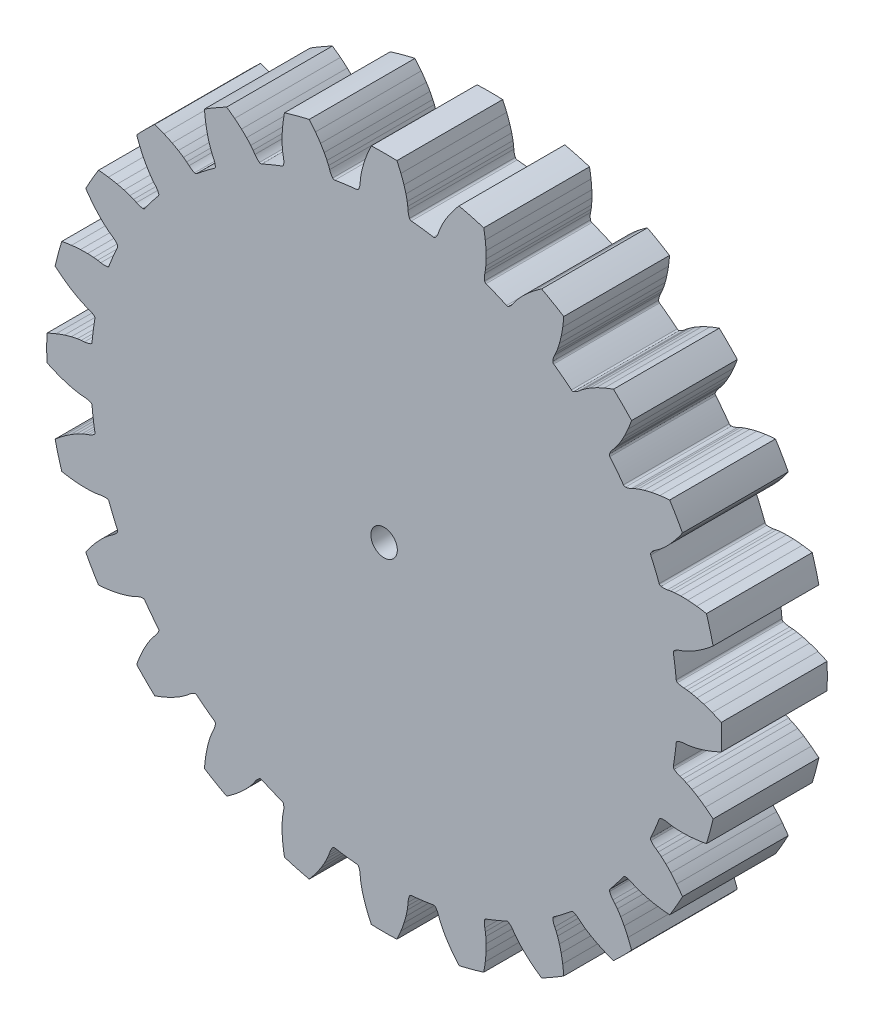
SolidWorks part; units mm, degrees
ref_plane "Front Plane" through (0, 0, 0) normal (0, 0, 1) x (1, 0, 0)
ref_plane "Top Plane" through (0, 0, 0) normal (0, 1, 0) x (1, 0, 0)
ref_plane "Right Plane" through (0, 0, 0) normal (1, 0, 0) x (0, 0, -1)
sketch "Model" plane through (0, 0, 0) normal (0, 0, 1) x (1, 0, 0)
  arc A1 (34.9181, -4.5971) -> (35.0673, -3.2696) centre (0, 0) ccw
  arc A2 (35.2278, -3.0481) -> (35.0673, -3.2696) centre (35.3347, -3.2945) ccw
  arc A3 (35.9833, -2.8721) -> (35.2278, -3.0481) centre (36.0877, -5.0299) ccw
  arc A4 (35.9833, -2.8721) -> (36.3636, -2.8405) centre (35.7172, 2.6237) ccw
  arc A5 (36.3636, -2.8405) -> (36.8336, -2.7716) centre (35.3622, 5.6245) ccw
  arc A6 (36.8336, -2.7716) -> (37.5555, -2.6174) centre (35.1043, 7.0963) ccw
  arc A7 (37.5555, -2.6174) -> (38.3737, -2.3829) centre (34.2966, 10.2971) ccw
  arc A8 (38.3737, -2.3829) -> (39.3866, -2.0164) centre (33.8084, 11.8154) ccw
  arc A9 (39.3866, -2.0164) -> (40.4752, -1.5354) centre (32.5769, 14.869) ccw
  arc A10 (40.4752, -1.5354) -> (40.4752, 1.5354) centre (0, 0) ccw
  arc A11 (40.4752, 1.5354) -> (39.3866, 2.0164) centre (32.5769, -14.869) ccw
  arc A12 (39.3866, 2.0164) -> (38.3737, 2.3829) centre (33.8084, -11.8154) ccw
  arc A13 (38.3737, 2.3829) -> (37.5555, 2.6174) centre (34.2966, -10.2971) ccw
  arc A14 (37.5555, 2.6174) -> (36.8336, 2.7716) centre (35.1043, -7.0963) ccw
  arc A15 (36.8336, 2.7716) -> (36.3636, 2.8405) centre (35.3622, -5.6245) ccw
  arc A16 (36.3636, 2.8405) -> (35.9833, 2.8721) centre (35.7172, -2.6237) ccw
  arc A17 (35.2278, 3.0481) -> (35.9833, 2.8721) centre (36.0877, 5.0299) ccw
  arc A18 (35.0673, 3.2696) -> (35.2278, 3.0481) centre (35.3347, 3.2945) ccw
  arc A19 (35.0673, 3.2696) -> (34.7187, 5.9179) centre (0, 0) ccw
  arc A20 (34.8164, 6.1734) -> (34.7187, 5.9179) centre (34.9834, 5.9631) ccw
  arc A21 (35.5005, 6.5389) -> (34.8164, 6.1734) centre (36.1599, 4.4817) ccw
  arc A22 (35.5005, 6.5389) -> (35.8597, 6.6679) centre (33.8211, 11.7785) ccw
  arc A23 (35.8597, 6.6679) -> (36.2958, 6.8561) centre (32.7015, 14.5853) ccw
  arc A24 (36.2958, 6.8561) -> (36.9533, 7.1918) centre (32.0715, 15.9402) ccw
  arc A25 (36.9533, 7.1918) -> (37.6829, 7.6301) centre (30.4629, 18.8229) ccw
  arc A26 (37.6829, 7.6301) -> (38.5664, 8.2463) centre (29.5984, 20.1631) ccw
  arc A27 (38.5664, 8.2463) -> (39.4934, 8.9927) centre (27.6185, 22.7939) ccw
  arc A28 (39.4934, 8.9927) -> (38.6987, 11.9589) centre (0, 0) ccw
  arc A29 (38.6987, 11.9589) -> (37.5227, 12.1417) centre (35.3153, -5.9309) ccw
  arc A30 (37.5227, 12.1417) -> (36.4494, 12.2336) centre (35.7145, -2.6625) ccw
  arc A31 (36.4494, 12.2336) -> (35.5984, 12.2483) centre (35.7931, -1.0696) ccw
  arc A32 (35.5984, 12.2483) -> (34.8612, 12.2104) centre (35.7448, 2.2311) ccw
  arc A33 (34.8612, 12.2104) -> (34.3894, 12.1553) centre (35.613, 3.7195) ccw
  arc A34 (34.3894, 12.1553) -> (34.0138, 12.0874) centre (35.1792, 6.71) ccw
  arc A35 (33.2386, 12.0619) -> (34.0138, 12.0874) centre (33.5562, 14.1987) ccw
  arc A36 (33.0262, 12.2343) -> (33.2386, 12.0619) centre (33.2781, 12.3275) ccw
  arc A37 (33.0262, 12.2343) -> (32.004, 14.7021) centre (0, 0) ccw
  arc A38 (32.0323, 14.9742) -> (32.004, 14.7021) centre (32.248, 14.8142) ccw
  arc A39 (32.5985, 15.5043) -> (32.0323, 14.9742) centre (33.7678, 13.6878) ccw
  arc A40 (32.5985, 15.5043) -> (32.912, 15.7219) centre (29.6202, 20.1308) ccw
  arc A41 (32.912, 15.7219) -> (33.2846, 16.0165) centre (27.8123, 22.5521) ccw
  arc A42 (33.2846, 16.0165) -> (33.8327, 16.511) centre (26.853, 23.6978) ccw
  arc A43 (33.8327, 16.511) -> (34.4241, 17.1232) centre (24.5532, 26.0659) ccw
  arc A44 (34.4241, 17.1232) -> (35.118, 17.9471) centre (23.3712, 27.1366) ccw
  arc A45 (35.118, 17.9471) -> (35.8203, 18.9079) centre (20.7779, 29.1654) ccw
  arc A46 (35.8203, 18.9079) -> (34.2849, 21.5673) centre (0, 0) ccw
  arc A47 (34.2849, 21.5673) -> (33.1016, 21.4395) centre (35.647, 3.4115) ccw
  arc A48 (33.1016, 21.4395) -> (32.0412, 21.2505) centre (35.1866, 6.6718) ccw
  arc A49 (32.0412, 21.2505) -> (31.2153, 21.0445) centre (34.8503, 8.2307) ccw
  arc A50 (31.2153, 21.0445) -> (30.513, 20.817) centre (33.9494, 11.4065) ccw
  arc A51 (30.513, 20.817) -> (30.0715, 20.6417) centre (33.4369, 12.8101) ccw
  arc A52 (30.0715, 20.6417) -> (29.7263, 20.479) centre (32.2438, 15.5865) ccw
  arc A53 (28.9841, 20.2537) -> (29.7263, 20.479) centre (28.7379, 22.3999) ccw
  arc A54 (28.7344, 20.3652) -> (28.9841, 20.2537) centre (28.9535, 20.5205) ccw
  arc A55 (28.7344, 20.3652) -> (27.1083, 22.4844) centre (0, 0) ccw
  arc A56 (27.0652, 22.7545) -> (27.1083, 22.4844) centre (27.315, 22.6559) ccw
  arc A57 (27.4749, 23.4131) -> (27.0652, 22.7545) centre (29.0746, 21.9612) ccw
  arc A58 (27.4749, 23.4131) -> (27.7215, 23.7044) centre (23.4007, 27.1111) ccw
  arc A59 (27.7215, 23.7044) -> (28.0051, 24.0855) centre (21.0277, 28.982) ccw
  arc A60 (28.0051, 24.0855) -> (28.4066, 24.7049) centre (19.8046, 29.8404) ccw
  arc A61 (28.4066, 24.7049) -> (28.8193, 25.4493) centre (16.9702, 31.5325) ccw
  arc A62 (28.8193, 25.4493) -> (29.2763, 26.4247) centre (15.5514, 32.2609) ccw
  arc A63 (29.2763, 26.4247) -> (29.706, 27.5346) centre (12.5214, 33.5494) ccw
  arc A64 (29.706, 27.5346) -> (27.5346, 29.706) centre (0, 0) ccw
  arc A65 (27.5346, 29.706) -> (26.4247, 29.2763) centre (33.5494, 12.5214) ccw
  arc A66 (26.4247, 29.2763) -> (25.4493, 28.8193) centre (32.2609, 15.5514) ccw
  arc A67 (25.4493, 28.8193) -> (24.7049, 28.4066) centre (31.5325, 16.9702) ccw
  arc A68 (24.7049, 28.4066) -> (24.0855, 28.0051) centre (29.8404, 19.8046) ccw
  arc A69 (24.0855, 28.0051) -> (23.7044, 27.7215) centre (28.982, 21.0277) ccw
  arc A70 (23.7044, 27.7215) -> (23.4131, 27.4749) centre (27.1111, 23.4007) ccw
  arc A71 (22.7545, 27.0652) -> (23.4131, 27.4749) centre (21.9612, 29.0746) ccw
  arc A72 (22.4844, 27.1083) -> (22.7545, 27.0652) centre (22.6559, 27.315) ccw
  arc A73 (22.4844, 27.1083) -> (20.3652, 28.7344) centre (0, 0) ccw
  arc A74 (20.2537, 28.9841) -> (20.3652, 28.7344) centre (20.5205, 28.9535) ccw
  arc A75 (20.479, 29.7263) -> (20.2537, 28.9841) centre (22.3999, 28.7379) ccw
  arc A76 (20.479, 29.7263) -> (20.6417, 30.0715) centre (15.5865, 32.2438) ccw
  arc A77 (20.6417, 30.0715) -> (20.817, 30.513) centre (12.8101, 33.4369) ccw
  arc A78 (20.817, 30.513) -> (21.0445, 31.2153) centre (11.4065, 33.9494) ccw
  arc A79 (21.0445, 31.2153) -> (21.2505, 32.0412) centre (8.2307, 34.8503) ccw
  arc A80 (21.2505, 32.0412) -> (21.4395, 33.1016) centre (6.6718, 35.1866) ccw
  arc A81 (21.4395, 33.1016) -> (21.5673, 34.2849) centre (3.4115, 35.647) ccw
  arc A82 (21.5673, 34.2849) -> (18.9079, 35.8203) centre (0, 0) ccw
  arc A83 (18.9079, 35.8203) -> (17.9471, 35.118) centre (29.1654, 20.7779) ccw
  arc A84 (17.9471, 35.118) -> (17.1232, 34.4241) centre (27.1366, 23.3712) ccw
  arc A85 (17.1232, 34.4241) -> (16.511, 33.8327) centre (26.0659, 24.5532) ccw
  arc A86 (16.511, 33.8327) -> (16.0165, 33.2846) centre (23.6978, 26.853) ccw
  arc A87 (16.0165, 33.2846) -> (15.7219, 32.912) centre (22.5521, 27.8123) ccw
  arc A88 (15.7219, 32.912) -> (15.5043, 32.5985) centre (20.1308, 29.6202) ccw
  arc A89 (14.9742, 32.0323) -> (15.5043, 32.5985) centre (13.6878, 33.7678) ccw
  arc A90 (14.7021, 32.004) -> (14.9742, 32.0323) centre (14.8142, 32.248) ccw
  arc A91 (14.7021, 32.004) -> (12.2343, 33.0262) centre (0, 0) ccw
  arc A92 (12.0619, 33.2386) -> (12.2343, 33.0262) centre (12.3275, 33.2781) ccw
  arc A93 (12.0874, 34.0138) -> (12.0619, 33.2386) centre (14.1987, 33.5562) ccw
  arc A94 (12.0874, 34.0138) -> (12.1553, 34.3894) centre (6.71, 35.1792) ccw
  arc A95 (12.1553, 34.3894) -> (12.2104, 34.8612) centre (3.7195, 35.613) ccw
  arc A96 (12.2104, 34.8612) -> (12.2483, 35.5984) centre (2.2311, 35.7448) ccw
  arc A97 (12.2483, 35.5984) -> (12.2336, 36.4494) centre (-1.0696, 35.7931) ccw
  arc A98 (12.2336, 36.4494) -> (12.1417, 37.5227) centre (-2.6625, 35.7145) ccw
  arc A99 (12.1417, 37.5227) -> (11.9589, 38.6987) centre (-5.9309, 35.3153) ccw
  arc A100 (11.9589, 38.6987) -> (8.9927, 39.4934) centre (0, 0) ccw
  arc A101 (8.9927, 39.4934) -> (8.2463, 38.5664) centre (22.7939, 27.6185) ccw
  arc A102 (8.2463, 38.5664) -> (7.6301, 37.6829) centre (20.1631, 29.5984) ccw
  arc A103 (7.6301, 37.6829) -> (7.1918, 36.9533) centre (18.8229, 30.4629) ccw
  arc A104 (7.1918, 36.9533) -> (6.8561, 36.2958) centre (15.9402, 32.0715) ccw
  arc A105 (6.8561, 36.2958) -> (6.6679, 35.8597) centre (14.5853, 32.7015) ccw
  arc A106 (6.6679, 35.8597) -> (6.5389, 35.5005) centre (11.7785, 33.8211) ccw
  arc A107 (6.1734, 34.8164) -> (6.5389, 35.5005) centre (4.4817, 36.1599) ccw
  arc A108 (5.9179, 34.7187) -> (6.1734, 34.8164) centre (5.9631, 34.9834) ccw
  arc A109 (5.9179, 34.7187) -> (3.2696, 35.0673) centre (0, 0) ccw
  arc A110 (3.0481, 35.2278) -> (3.2696, 35.0673) centre (3.2945, 35.3347) ccw
  arc A111 (2.8721, 35.9833) -> (3.0481, 35.2278) centre (5.0299, 36.0877) ccw
  arc A112 (2.8721, 35.9833) -> (2.8405, 36.3636) centre (-2.6237, 35.7172) ccw
  arc A113 (2.8405, 36.3636) -> (2.7716, 36.8336) centre (-5.6245, 35.3622) ccw
  arc A114 (2.7716, 36.8336) -> (2.6174, 37.5555) centre (-7.0963, 35.1043) ccw
  arc A115 (2.6174, 37.5555) -> (2.3829, 38.3737) centre (-10.2971, 34.2966) ccw
  arc A116 (2.3829, 38.3737) -> (2.0164, 39.3866) centre (-11.8154, 33.8084) ccw
  arc A117 (2.0164, 39.3866) -> (1.5354, 40.4752) centre (-14.869, 32.5769) ccw
  arc A118 (1.5354, 40.4752) -> (-1.5354, 40.4752) centre (0, 0) ccw
  arc A119 (-1.5354, 40.4752) -> (-2.0164, 39.3866) centre (14.869, 32.5769) ccw
  arc A120 (-2.0164, 39.3866) -> (-2.3829, 38.3737) centre (11.8154, 33.8084) ccw
  arc A121 (-2.3829, 38.3737) -> (-2.6174, 37.5555) centre (10.2971, 34.2966) ccw
  arc A122 (-2.6174, 37.5555) -> (-2.7716, 36.8336) centre (7.0963, 35.1043) ccw
  arc A123 (-2.7716, 36.8336) -> (-2.8405, 36.3636) centre (5.6245, 35.3622) ccw
  arc A124 (-2.8405, 36.3636) -> (-2.8721, 35.9833) centre (2.6237, 35.7172) ccw
  arc A125 (-3.0481, 35.2278) -> (-2.8721, 35.9833) centre (-5.0299, 36.0877) ccw
  arc A126 (-3.2696, 35.0673) -> (-3.0481, 35.2278) centre (-3.2945, 35.3347) ccw
  arc A127 (-3.2696, 35.0673) -> (-5.9179, 34.7187) centre (0, 0) ccw
  arc A128 (-6.1734, 34.8164) -> (-5.9179, 34.7187) centre (-5.9631, 34.9834) ccw
  arc A129 (-6.5389, 35.5005) -> (-6.1734, 34.8164) centre (-4.4817, 36.1599) ccw
  arc A130 (-6.5389, 35.5005) -> (-6.6679, 35.8597) centre (-11.7785, 33.8211) ccw
  arc A131 (-6.6679, 35.8597) -> (-6.8561, 36.2958) centre (-14.5853, 32.7015) ccw
  arc A132 (-6.8561, 36.2958) -> (-7.1918, 36.9533) centre (-15.9402, 32.0715) ccw
  arc A133 (-7.1918, 36.9533) -> (-7.6301, 37.6829) centre (-18.8229, 30.4629) ccw
  arc A134 (-7.6301, 37.6829) -> (-8.2463, 38.5664) centre (-20.1631, 29.5984) ccw
  arc A135 (-8.2463, 38.5664) -> (-8.9927, 39.4934) centre (-22.7939, 27.6185) ccw
  arc A136 (-8.9927, 39.4934) -> (-11.9589, 38.6987) centre (0, 0) ccw
  arc A137 (-11.9589, 38.6987) -> (-12.1417, 37.5227) centre (5.9309, 35.3153) ccw
  arc A138 (-12.1417, 37.5227) -> (-12.2336, 36.4494) centre (2.6625, 35.7145) ccw
  arc A139 (-12.2336, 36.4494) -> (-12.2483, 35.5984) centre (1.0696, 35.7931) ccw
  arc A140 (-12.2483, 35.5984) -> (-12.2104, 34.8612) centre (-2.2311, 35.7448) ccw
  arc A141 (-12.2104, 34.8612) -> (-12.1553, 34.3894) centre (-3.7195, 35.613) ccw
  arc A142 (-12.1553, 34.3894) -> (-12.0874, 34.0138) centre (-6.71, 35.1792) ccw
  arc A143 (-12.0619, 33.2386) -> (-12.0874, 34.0138) centre (-14.1987, 33.5562) ccw
  arc A144 (-12.2343, 33.0262) -> (-12.0619, 33.2386) centre (-12.3275, 33.2781) ccw
  arc A145 (-12.2343, 33.0262) -> (-14.7021, 32.004) centre (0, 0) ccw
  arc A146 (-14.9742, 32.0323) -> (-14.7021, 32.004) centre (-14.8142, 32.248) ccw
  arc A147 (-15.5043, 32.5985) -> (-14.9742, 32.0323) centre (-13.6878, 33.7678) ccw
  arc A148 (-15.5043, 32.5985) -> (-15.7219, 32.912) centre (-20.1308, 29.6202) ccw
  arc A149 (-15.7219, 32.912) -> (-16.0165, 33.2846) centre (-22.5521, 27.8123) ccw
  arc A150 (-16.0165, 33.2846) -> (-16.511, 33.8327) centre (-23.6978, 26.853) ccw
  arc A151 (-16.511, 33.8327) -> (-17.1232, 34.4241) centre (-26.0659, 24.5532) ccw
  arc A152 (-17.1232, 34.4241) -> (-17.9471, 35.118) centre (-27.1366, 23.3712) ccw
  arc A153 (-17.9471, 35.118) -> (-18.9079, 35.8203) centre (-29.1654, 20.7779) ccw
  arc A154 (-18.9079, 35.8203) -> (-21.5673, 34.2849) centre (0, 0) ccw
  arc A155 (-21.5673, 34.2849) -> (-21.4395, 33.1016) centre (-3.4115, 35.647) ccw
  arc A156 (-21.4395, 33.1016) -> (-21.2505, 32.0412) centre (-6.6718, 35.1866) ccw
  arc A157 (-21.2505, 32.0412) -> (-21.0445, 31.2153) centre (-8.2307, 34.8503) ccw
  arc A158 (-21.0445, 31.2153) -> (-20.817, 30.513) centre (-11.4065, 33.9494) ccw
  arc A159 (-20.817, 30.513) -> (-20.6417, 30.0715) centre (-12.8101, 33.4369) ccw
  arc A160 (-20.6417, 30.0715) -> (-20.479, 29.7263) centre (-15.5865, 32.2438) ccw
  arc A161 (-20.2537, 28.9841) -> (-20.479, 29.7263) centre (-22.3999, 28.7379) ccw
  arc A162 (-20.3652, 28.7344) -> (-20.2537, 28.9841) centre (-20.5205, 28.9535) ccw
  arc A163 (-20.3652, 28.7344) -> (-22.4844, 27.1083) centre (0, 0) ccw
  arc A164 (-22.7545, 27.0652) -> (-22.4844, 27.1083) centre (-22.6559, 27.315) ccw
  arc A165 (-23.4131, 27.4749) -> (-22.7545, 27.0652) centre (-21.9612, 29.0746) ccw
  arc A166 (-23.4131, 27.4749) -> (-23.7044, 27.7215) centre (-27.1111, 23.4007) ccw
  arc A167 (-23.7044, 27.7215) -> (-24.0855, 28.0051) centre (-28.982, 21.0277) ccw
  arc A168 (-24.0855, 28.0051) -> (-24.7049, 28.4066) centre (-29.8404, 19.8046) ccw
  arc A169 (-24.7049, 28.4066) -> (-25.4493, 28.8193) centre (-31.5325, 16.9702) ccw
  arc A170 (-25.4493, 28.8193) -> (-26.4247, 29.2763) centre (-32.2609, 15.5514) ccw
  arc A171 (-26.4247, 29.2763) -> (-27.5346, 29.706) centre (-33.5494, 12.5214) ccw
  arc A172 (-27.5346, 29.706) -> (-29.706, 27.5346) centre (0, 0) ccw
  arc A173 (-29.706, 27.5346) -> (-29.2763, 26.4247) centre (-12.5214, 33.5494) ccw
  arc A174 (-29.2763, 26.4247) -> (-28.8193, 25.4493) centre (-15.5514, 32.2609) ccw
  arc A175 (-28.8193, 25.4493) -> (-28.4066, 24.7049) centre (-16.9702, 31.5325) ccw
  arc A176 (-28.4066, 24.7049) -> (-28.0051, 24.0855) centre (-19.8046, 29.8404) ccw
  arc A177 (-28.0051, 24.0855) -> (-27.7215, 23.7044) centre (-21.0277, 28.982) ccw
  arc A178 (-27.7215, 23.7044) -> (-27.4749, 23.4131) centre (-23.4007, 27.1111) ccw
  arc A179 (-27.0652, 22.7545) -> (-27.4749, 23.4131) centre (-29.0746, 21.9612) ccw
  arc A180 (-27.1083, 22.4844) -> (-27.0652, 22.7545) centre (-27.315, 22.6559) ccw
  arc A181 (-27.1083, 22.4844) -> (-28.7344, 20.3652) centre (0, 0) ccw
  arc A182 (-28.9841, 20.2537) -> (-28.7344, 20.3652) centre (-28.9535, 20.5205) ccw
  arc A183 (-29.7263, 20.479) -> (-28.9841, 20.2537) centre (-28.7379, 22.3999) ccw
  arc A184 (-29.7263, 20.479) -> (-30.0715, 20.6417) centre (-32.2438, 15.5865) ccw
  arc A185 (-30.0715, 20.6417) -> (-30.513, 20.817) centre (-33.4369, 12.8101) ccw
  arc A186 (-30.513, 20.817) -> (-31.2153, 21.0445) centre (-33.9494, 11.4065) ccw
  arc A187 (-31.2153, 21.0445) -> (-32.0412, 21.2505) centre (-34.8503, 8.2307) ccw
  arc A188 (-32.0412, 21.2505) -> (-33.1016, 21.4395) centre (-35.1866, 6.6718) ccw
  arc A189 (-33.1016, 21.4395) -> (-34.2849, 21.5673) centre (-35.647, 3.4115) ccw
  arc A190 (-34.2849, 21.5673) -> (-35.8203, 18.9079) centre (0, 0) ccw
  arc A191 (-35.8203, 18.9079) -> (-35.118, 17.9471) centre (-20.7779, 29.1654) ccw
  arc A192 (-35.118, 17.9471) -> (-34.4241, 17.1232) centre (-23.3712, 27.1366) ccw
  arc A193 (-34.4241, 17.1232) -> (-33.8327, 16.511) centre (-24.5532, 26.0659) ccw
  arc A194 (-33.8327, 16.511) -> (-33.2846, 16.0165) centre (-26.853, 23.6978) ccw
  arc A195 (-33.2846, 16.0165) -> (-32.912, 15.7219) centre (-27.8123, 22.5521) ccw
  arc A196 (-32.912, 15.7219) -> (-32.5985, 15.5043) centre (-29.6202, 20.1308) ccw
  arc A197 (-32.0323, 14.9742) -> (-32.5985, 15.5043) centre (-33.7678, 13.6878) ccw
  arc A198 (-32.004, 14.7021) -> (-32.0323, 14.9742) centre (-32.248, 14.8142) ccw
  arc A199 (-32.004, 14.7021) -> (-33.0262, 12.2343) centre (0, 0) ccw
  arc A200 (-33.2386, 12.0619) -> (-33.0262, 12.2343) centre (-33.2781, 12.3275) ccw
  arc A201 (-34.0138, 12.0874) -> (-33.2386, 12.0619) centre (-33.5562, 14.1987) ccw
  arc A202 (-34.0138, 12.0874) -> (-34.3894, 12.1553) centre (-35.1792, 6.71) ccw
  arc A203 (-34.3894, 12.1553) -> (-34.8612, 12.2104) centre (-35.613, 3.7195) ccw
  arc A204 (-34.8612, 12.2104) -> (-35.5984, 12.2483) centre (-35.7448, 2.2311) ccw
  arc A205 (-35.5984, 12.2483) -> (-36.4494, 12.2336) centre (-35.7931, -1.0696) ccw
  arc A206 (-36.4494, 12.2336) -> (-37.5227, 12.1417) centre (-35.7145, -2.6625) ccw
  arc A207 (-37.5227, 12.1417) -> (-38.6987, 11.9589) centre (-35.3153, -5.9309) ccw
  arc A208 (-38.6987, 11.9589) -> (-39.4934, 8.9927) centre (0, 0) ccw
  arc A209 (-39.4934, 8.9927) -> (-38.5664, 8.2463) centre (-27.6185, 22.7939) ccw
  arc A210 (-38.5664, 8.2463) -> (-37.6829, 7.6301) centre (-29.5984, 20.1631) ccw
  arc A211 (-37.6829, 7.6301) -> (-36.9533, 7.1918) centre (-30.4629, 18.8229) ccw
  arc A212 (-36.9533, 7.1918) -> (-36.2958, 6.8561) centre (-32.0715, 15.9402) ccw
  arc A213 (-36.2958, 6.8561) -> (-35.8597, 6.6679) centre (-32.7015, 14.5853) ccw
  arc A214 (-35.8597, 6.6679) -> (-35.5005, 6.5389) centre (-33.8211, 11.7785) ccw
  arc A215 (-34.8164, 6.1734) -> (-35.5005, 6.5389) centre (-36.1599, 4.4817) ccw
  arc A216 (-34.7187, 5.9179) -> (-34.8164, 6.1734) centre (-34.9834, 5.9631) ccw
  arc A217 (-34.7187, 5.9179) -> (-35.0673, 3.2696) centre (0, 0) ccw
  arc A218 (-35.2278, 3.0481) -> (-35.0673, 3.2696) centre (-35.3347, 3.2945) ccw
  arc A219 (-35.9833, 2.8721) -> (-35.2278, 3.0481) centre (-36.0877, 5.0299) ccw
  arc A220 (-35.9833, 2.8721) -> (-36.3636, 2.8405) centre (-35.7172, -2.6237) ccw
  arc A221 (-36.3636, 2.8405) -> (-36.8336, 2.7716) centre (-35.3622, -5.6245) ccw
  arc A222 (-36.8336, 2.7716) -> (-37.5555, 2.6174) centre (-35.1043, -7.0963) ccw
  arc A223 (-37.5555, 2.6174) -> (-38.3737, 2.3829) centre (-34.2966, -10.2971) ccw
  arc A224 (-38.3737, 2.3829) -> (-39.3866, 2.0164) centre (-33.8084, -11.8154) ccw
  arc A225 (-39.3866, 2.0164) -> (-40.4752, 1.5354) centre (-32.5769, -14.869) ccw
  arc A226 (-40.4752, 1.5354) -> (-40.4752, -1.5354) centre (0, 0) ccw
  arc A227 (-40.4752, -1.5354) -> (-39.3866, -2.0164) centre (-32.5769, 14.869) ccw
  arc A228 (-39.3866, -2.0164) -> (-38.3737, -2.3829) centre (-33.8084, 11.8154) ccw
  arc A229 (-38.3737, -2.3829) -> (-37.5555, -2.6174) centre (-34.2966, 10.2971) ccw
  arc A230 (-37.5555, -2.6174) -> (-36.8336, -2.7716) centre (-35.1043, 7.0963) ccw
  arc A231 (-36.8336, -2.7716) -> (-36.3636, -2.8405) centre (-35.3622, 5.6245) ccw
  arc A232 (-36.3636, -2.8405) -> (-35.9833, -2.8721) centre (-35.7172, 2.6237) ccw
  arc A233 (-35.2278, -3.0481) -> (-35.9833, -2.8721) centre (-36.0877, -5.0299) ccw
  arc A234 (-35.0673, -3.2696) -> (-35.2278, -3.0481) centre (-35.3347, -3.2945) ccw
  arc A235 (-35.0673, -3.2696) -> (-34.7187, -5.9179) centre (0, 0) ccw
  arc A236 (-34.8164, -6.1734) -> (-34.7187, -5.9179) centre (-34.9834, -5.9631) ccw
  arc A237 (-35.5005, -6.5389) -> (-34.8164, -6.1734) centre (-36.1599, -4.4817) ccw
  arc A238 (-35.5005, -6.5389) -> (-35.8597, -6.6679) centre (-33.8211, -11.7785) ccw
  arc A239 (-35.8597, -6.6679) -> (-36.2958, -6.8561) centre (-32.7015, -14.5853) ccw
  arc A240 (-36.2958, -6.8561) -> (-36.9533, -7.1918) centre (-32.0715, -15.9402) ccw
  arc A241 (-36.9533, -7.1918) -> (-37.6829, -7.6301) centre (-30.4629, -18.8229) ccw
  arc A242 (-37.6829, -7.6301) -> (-38.5664, -8.2463) centre (-29.5984, -20.1631) ccw
  arc A243 (-38.5664, -8.2463) -> (-39.4934, -8.9927) centre (-27.6185, -22.7939) ccw
  arc A244 (-39.4934, -8.9927) -> (-38.6987, -11.9589) centre (0, 0) ccw
  arc A245 (-38.6987, -11.9589) -> (-37.5227, -12.1417) centre (-35.3153, 5.9309) ccw
  arc A246 (-37.5227, -12.1417) -> (-36.4494, -12.2336) centre (-35.7145, 2.6625) ccw
  arc A247 (-36.4494, -12.2336) -> (-35.5984, -12.2483) centre (-35.7931, 1.0696) ccw
  arc A248 (-35.5984, -12.2483) -> (-34.8612, -12.2104) centre (-35.7448, -2.2311) ccw
  arc A249 (-34.8612, -12.2104) -> (-34.3894, -12.1553) centre (-35.613, -3.7195) ccw
  arc A250 (-34.3894, -12.1553) -> (-34.0138, -12.0874) centre (-35.1792, -6.71) ccw
  arc A251 (-33.2386, -12.0619) -> (-34.0138, -12.0874) centre (-33.5562, -14.1987) ccw
  arc A252 (-33.0262, -12.2343) -> (-33.2386, -12.0619) centre (-33.2781, -12.3275) ccw
  arc A253 (-33.0262, -12.2343) -> (-32.004, -14.7021) centre (0, 0) ccw
  arc A254 (-32.0323, -14.9742) -> (-32.004, -14.7021) centre (-32.248, -14.8142) ccw
  arc A255 (-32.5985, -15.5043) -> (-32.0323, -14.9742) centre (-33.7678, -13.6878) ccw
  arc A256 (-32.5985, -15.5043) -> (-32.912, -15.7219) centre (-29.6202, -20.1308) ccw
  arc A257 (-32.912, -15.7219) -> (-33.2846, -16.0165) centre (-27.8123, -22.5521) ccw
  arc A258 (-33.2846, -16.0165) -> (-33.8327, -16.511) centre (-26.853, -23.6978) ccw
  arc A259 (-33.8327, -16.511) -> (-34.4241, -17.1232) centre (-24.5532, -26.0659) ccw
  arc A260 (-34.4241, -17.1232) -> (-35.118, -17.9471) centre (-23.3712, -27.1366) ccw
  arc A261 (-35.118, -17.9471) -> (-35.8203, -18.9079) centre (-20.7779, -29.1654) ccw
  arc A262 (-35.8203, -18.9079) -> (-34.2849, -21.5673) centre (0, 0) ccw
  arc A263 (-34.2849, -21.5673) -> (-33.1016, -21.4395) centre (-35.647, -3.4115) ccw
  arc A264 (-33.1016, -21.4395) -> (-32.0412, -21.2505) centre (-35.1866, -6.6718) ccw
  arc A265 (-32.0412, -21.2505) -> (-31.2153, -21.0445) centre (-34.8503, -8.2307) ccw
  arc A266 (-31.2153, -21.0445) -> (-30.513, -20.817) centre (-33.9494, -11.4065) ccw
  arc A267 (-30.513, -20.817) -> (-30.0715, -20.6417) centre (-33.4369, -12.8101) ccw
  arc A268 (-30.0715, -20.6417) -> (-29.7263, -20.479) centre (-32.2438, -15.5865) ccw
  arc A269 (-28.9841, -20.2537) -> (-29.7263, -20.479) centre (-28.7379, -22.3999) ccw
  arc A270 (-28.7344, -20.3652) -> (-28.9841, -20.2537) centre (-28.9535, -20.5205) ccw
  arc A271 (-28.7344, -20.3652) -> (-27.1083, -22.4844) centre (0, 0) ccw
  arc A272 (-27.0652, -22.7545) -> (-27.1083, -22.4844) centre (-27.315, -22.6559) ccw
  arc A273 (-27.4749, -23.4131) -> (-27.0652, -22.7545) centre (-29.0746, -21.9612) ccw
  arc A274 (-27.4749, -23.4131) -> (-27.7215, -23.7044) centre (-23.4007, -27.1111) ccw
  arc A275 (-27.7215, -23.7044) -> (-28.0051, -24.0855) centre (-21.0277, -28.982) ccw
  arc A276 (-28.0051, -24.0855) -> (-28.4066, -24.7049) centre (-19.8046, -29.8404) ccw
  arc A277 (-28.4066, -24.7049) -> (-28.8193, -25.4493) centre (-16.9702, -31.5325) ccw
  arc A278 (-28.8193, -25.4493) -> (-29.2763, -26.4247) centre (-15.5514, -32.2609) ccw
  arc A279 (-29.2763, -26.4247) -> (-29.706, -27.5346) centre (-12.5214, -33.5494) ccw
  arc A280 (-29.706, -27.5346) -> (-27.5346, -29.706) centre (0, 0) ccw
  arc A281 (-27.5346, -29.706) -> (-26.4247, -29.2763) centre (-33.5494, -12.5214) ccw
  arc A282 (-26.4247, -29.2763) -> (-25.4493, -28.8193) centre (-32.2609, -15.5514) ccw
  arc A283 (-25.4493, -28.8193) -> (-24.7049, -28.4066) centre (-31.5325, -16.9702) ccw
  arc A284 (-24.7049, -28.4066) -> (-24.0855, -28.0051) centre (-29.8404, -19.8046) ccw
  arc A285 (-24.0855, -28.0051) -> (-23.7044, -27.7215) centre (-28.982, -21.0277) ccw
  arc A286 (-23.7044, -27.7215) -> (-23.4131, -27.4749) centre (-27.1111, -23.4007) ccw
  arc A287 (-22.7545, -27.0652) -> (-23.4131, -27.4749) centre (-21.9612, -29.0746) ccw
  arc A288 (-22.4844, -27.1083) -> (-22.7545, -27.0652) centre (-22.6559, -27.315) ccw
  arc A289 (-22.4844, -27.1083) -> (-20.3652, -28.7344) centre (0, 0) ccw
  arc A290 (-20.2537, -28.9841) -> (-20.3652, -28.7344) centre (-20.5205, -28.9535) ccw
  arc A291 (-20.479, -29.7263) -> (-20.2537, -28.9841) centre (-22.3999, -28.7379) ccw
  arc A292 (-20.479, -29.7263) -> (-20.6417, -30.0715) centre (-15.5865, -32.2438) ccw
  arc A293 (-20.6417, -30.0715) -> (-20.817, -30.513) centre (-12.8101, -33.4369) ccw
  arc A294 (-20.817, -30.513) -> (-21.0445, -31.2153) centre (-11.4065, -33.9494) ccw
  arc A295 (-21.0445, -31.2153) -> (-21.2505, -32.0412) centre (-8.2307, -34.8503) ccw
  arc A296 (-21.2505, -32.0412) -> (-21.4395, -33.1016) centre (-6.6718, -35.1866) ccw
  arc A297 (-21.4395, -33.1016) -> (-21.5673, -34.2849) centre (-3.4115, -35.647) ccw
  arc A298 (-21.5673, -34.2849) -> (-18.9079, -35.8203) centre (0, 0) ccw
  arc A299 (-18.9079, -35.8203) -> (-17.9471, -35.118) centre (-29.1654, -20.7779) ccw
  arc A300 (-17.9471, -35.118) -> (-17.1232, -34.4241) centre (-27.1366, -23.3712) ccw
  arc A301 (-17.1232, -34.4241) -> (-16.511, -33.8327) centre (-26.0659, -24.5532) ccw
  arc A302 (-16.511, -33.8327) -> (-16.0165, -33.2846) centre (-23.6978, -26.853) ccw
  arc A303 (-16.0165, -33.2846) -> (-15.7219, -32.912) centre (-22.5521, -27.8123) ccw
  arc A304 (-15.7219, -32.912) -> (-15.5043, -32.5985) centre (-20.1308, -29.6202) ccw
  arc A305 (-14.9742, -32.0323) -> (-15.5043, -32.5985) centre (-13.6878, -33.7678) ccw
  arc A306 (-14.7021, -32.004) -> (-14.9742, -32.0323) centre (-14.8142, -32.248) ccw
  arc A307 (-14.7021, -32.004) -> (-12.2343, -33.0262) centre (0, 0) ccw
  arc A308 (-12.0619, -33.2386) -> (-12.2343, -33.0262) centre (-12.3275, -33.2781) ccw
  arc A309 (-12.0874, -34.0138) -> (-12.0619, -33.2386) centre (-14.1987, -33.5562) ccw
  arc A310 (-12.0874, -34.0138) -> (-12.1553, -34.3894) centre (-6.71, -35.1792) ccw
  arc A311 (-12.1553, -34.3894) -> (-12.2104, -34.8612) centre (-3.7195, -35.613) ccw
  arc A312 (-12.2104, -34.8612) -> (-12.2483, -35.5984) centre (-2.2311, -35.7448) ccw
  arc A313 (-12.2483, -35.5984) -> (-12.2336, -36.4494) centre (1.0696, -35.7931) ccw
  arc A314 (-12.2336, -36.4494) -> (-12.1417, -37.5227) centre (2.6625, -35.7145) ccw
  arc A315 (-12.1417, -37.5227) -> (-11.9589, -38.6987) centre (5.9309, -35.3153) ccw
  arc A316 (-11.9589, -38.6987) -> (-8.9927, -39.4934) centre (0, 0) ccw
  arc A317 (-8.9927, -39.4934) -> (-8.2463, -38.5664) centre (-22.7939, -27.6185) ccw
  arc A318 (-8.2463, -38.5664) -> (-7.6301, -37.6829) centre (-20.1631, -29.5984) ccw
  arc A319 (-7.6301, -37.6829) -> (-7.1918, -36.9533) centre (-18.8229, -30.4629) ccw
  arc A320 (-7.1918, -36.9533) -> (-6.8561, -36.2958) centre (-15.9402, -32.0715) ccw
  arc A321 (-6.8561, -36.2958) -> (-6.6679, -35.8597) centre (-14.5853, -32.7015) ccw
  arc A322 (-6.6679, -35.8597) -> (-6.5389, -35.5005) centre (-11.7785, -33.8211) ccw
  arc A323 (-6.1734, -34.8164) -> (-6.5389, -35.5005) centre (-4.4817, -36.1599) ccw
  arc A324 (-5.9179, -34.7187) -> (-6.1734, -34.8164) centre (-5.9631, -34.9834) ccw
  arc A325 (-5.9179, -34.7187) -> (-3.2696, -35.0673) centre (0, 0) ccw
  arc A326 (-3.0481, -35.2278) -> (-3.2696, -35.0673) centre (-3.2945, -35.3347) ccw
  arc A327 (-2.8721, -35.9833) -> (-3.0481, -35.2278) centre (-5.0299, -36.0877) ccw
  arc A328 (-2.8721, -35.9833) -> (-2.8405, -36.3636) centre (2.6237, -35.7172) ccw
  arc A329 (-2.8405, -36.3636) -> (-2.7716, -36.8336) centre (5.6245, -35.3622) ccw
  arc A330 (-2.7716, -36.8336) -> (-2.6174, -37.5555) centre (7.0963, -35.1043) ccw
  arc A331 (-2.6174, -37.5555) -> (-2.3829, -38.3737) centre (10.2971, -34.2966) ccw
  arc A332 (-2.3829, -38.3737) -> (-2.0164, -39.3866) centre (11.8154, -33.8084) ccw
  arc A333 (-2.0164, -39.3866) -> (-1.5354, -40.4752) centre (14.869, -32.5769) ccw
  arc A334 (-1.5354, -40.4752) -> (1.5354, -40.4752) centre (0, 0) ccw
  arc A335 (1.5354, -40.4752) -> (2.0164, -39.3866) centre (-14.869, -32.5769) ccw
  arc A336 (2.0164, -39.3866) -> (2.3829, -38.3737) centre (-11.8154, -33.8084) ccw
  arc A337 (2.3829, -38.3737) -> (2.6174, -37.5555) centre (-10.2971, -34.2966) ccw
  arc A338 (2.6174, -37.5555) -> (2.7716, -36.8336) centre (-7.0963, -35.1043) ccw
  arc A339 (2.7716, -36.8336) -> (2.8405, -36.3636) centre (-5.6245, -35.3622) ccw
  arc A340 (2.8405, -36.3636) -> (2.8721, -35.9833) centre (-2.6237, -35.7172) ccw
  arc A341 (3.0481, -35.2278) -> (2.8721, -35.9833) centre (5.0299, -36.0877) ccw
  arc A342 (3.2696, -35.0673) -> (3.0481, -35.2278) centre (3.2945, -35.3347) ccw
  arc A343 (3.2696, -35.0673) -> (5.9179, -34.7187) centre (0, 0) ccw
  arc A344 (6.1734, -34.8164) -> (5.9179, -34.7187) centre (5.9631, -34.9834) ccw
  arc A345 (6.5389, -35.5005) -> (6.1734, -34.8164) centre (4.4817, -36.1599) ccw
  arc A346 (6.5389, -35.5005) -> (6.6679, -35.8597) centre (11.7785, -33.8211) ccw
  arc A347 (6.6679, -35.8597) -> (6.8561, -36.2958) centre (14.5853, -32.7015) ccw
  arc A348 (6.8561, -36.2958) -> (7.1918, -36.9533) centre (15.9402, -32.0715) ccw
  arc A349 (7.1918, -36.9533) -> (7.6301, -37.6829) centre (18.8229, -30.4629) ccw
  arc A350 (7.6301, -37.6829) -> (8.2463, -38.5664) centre (20.1631, -29.5984) ccw
  arc A351 (8.2463, -38.5664) -> (8.9927, -39.4934) centre (22.7939, -27.6185) ccw
  arc A352 (8.9927, -39.4934) -> (11.9589, -38.6987) centre (0, 0) ccw
  arc A353 (11.9589, -38.6987) -> (12.1417, -37.5227) centre (-5.9309, -35.3153) ccw
  arc A354 (12.1417, -37.5227) -> (12.2336, -36.4494) centre (-2.6625, -35.7145) ccw
  arc A355 (12.2336, -36.4494) -> (12.2483, -35.5984) centre (-1.0696, -35.7931) ccw
  arc A356 (12.2483, -35.5984) -> (12.2104, -34.8612) centre (2.2311, -35.7448) ccw
  arc A357 (12.2104, -34.8612) -> (12.1553, -34.3894) centre (3.7195, -35.613) ccw
  arc A358 (12.1553, -34.3894) -> (12.0874, -34.0138) centre (6.71, -35.1792) ccw
  arc A359 (12.0619, -33.2386) -> (12.0874, -34.0138) centre (14.1987, -33.5562) ccw
  arc A360 (12.2343, -33.0262) -> (12.0619, -33.2386) centre (12.3275, -33.2781) ccw
  arc A361 (12.2343, -33.0262) -> (14.7021, -32.004) centre (0, 0) ccw
  arc A362 (14.9742, -32.0323) -> (14.7021, -32.004) centre (14.8142, -32.248) ccw
  arc A363 (15.5043, -32.5985) -> (14.9742, -32.0323) centre (13.6878, -33.7678) ccw
  arc A364 (15.5043, -32.5985) -> (15.7219, -32.912) centre (20.1308, -29.6202) ccw
  arc A365 (15.7219, -32.912) -> (16.0165, -33.2846) centre (22.5521, -27.8123) ccw
  arc A366 (16.0165, -33.2846) -> (16.511, -33.8327) centre (23.6978, -26.853) ccw
  arc A367 (16.511, -33.8327) -> (17.1232, -34.4241) centre (26.0659, -24.5532) ccw
  arc A368 (17.1232, -34.4241) -> (17.9471, -35.118) centre (27.1366, -23.3712) ccw
  arc A369 (17.9471, -35.118) -> (18.9079, -35.8203) centre (29.1654, -20.7779) ccw
  arc A370 (18.9079, -35.8203) -> (21.5673, -34.2849) centre (0, 0) ccw
  arc A371 (21.5673, -34.2849) -> (21.4395, -33.1016) centre (3.4115, -35.647) ccw
  arc A372 (21.4395, -33.1016) -> (21.2505, -32.0412) centre (6.6718, -35.1866) ccw
  arc A373 (21.2505, -32.0412) -> (21.0445, -31.2153) centre (8.2307, -34.8503) ccw
  arc A374 (21.0445, -31.2153) -> (20.817, -30.513) centre (11.4065, -33.9494) ccw
  arc A375 (20.817, -30.513) -> (20.6417, -30.0715) centre (12.8101, -33.4369) ccw
  arc A376 (20.6417, -30.0715) -> (20.479, -29.7263) centre (15.5865, -32.2438) ccw
  arc A377 (20.2537, -28.9841) -> (20.479, -29.7263) centre (22.3999, -28.7379) ccw
  arc A378 (20.3652, -28.7344) -> (20.2537, -28.9841) centre (20.5205, -28.9535) ccw
  arc A379 (20.3652, -28.7344) -> (22.4844, -27.1083) centre (0, 0) ccw
  arc A380 (22.7545, -27.0652) -> (22.4844, -27.1083) centre (22.6559, -27.315) ccw
  arc A381 (23.4131, -27.4749) -> (22.7545, -27.0652) centre (21.9612, -29.0746) ccw
  arc A382 (23.4131, -27.4749) -> (23.7044, -27.7215) centre (27.1111, -23.4007) ccw
  arc A383 (23.7044, -27.7215) -> (24.0855, -28.0051) centre (28.982, -21.0277) ccw
  arc A384 (24.0855, -28.0051) -> (24.7049, -28.4066) centre (29.8404, -19.8046) ccw
  arc A385 (24.7049, -28.4066) -> (25.4493, -28.8193) centre (31.5325, -16.9702) ccw
  arc A386 (25.4493, -28.8193) -> (26.4247, -29.2763) centre (32.2609, -15.5514) ccw
  arc A387 (26.4247, -29.2763) -> (27.5346, -29.706) centre (33.5494, -12.5214) ccw
  arc A388 (27.5346, -29.706) -> (29.706, -27.5346) centre (0, 0) ccw
  arc A389 (29.706, -27.5346) -> (29.2763, -26.4247) centre (12.5214, -33.5494) ccw
  arc A390 (29.2763, -26.4247) -> (28.8193, -25.4493) centre (15.5514, -32.2609) ccw
  arc A391 (28.8193, -25.4493) -> (28.4066, -24.7049) centre (16.9702, -31.5325) ccw
  arc A392 (28.4066, -24.7049) -> (28.0051, -24.0855) centre (19.8046, -29.8404) ccw
  arc A393 (28.0051, -24.0855) -> (27.7215, -23.7044) centre (21.0277, -28.982) ccw
  arc A394 (27.7215, -23.7044) -> (27.4749, -23.4131) centre (23.4007, -27.1111) ccw
  arc A395 (27.0652, -22.7545) -> (27.4749, -23.4131) centre (29.0746, -21.9612) ccw
  arc A396 (27.1083, -22.4844) -> (27.0652, -22.7545) centre (27.315, -22.6559) ccw
  arc A397 (27.1083, -22.4844) -> (28.7344, -20.3652) centre (0, 0) ccw
  arc A398 (28.9841, -20.2537) -> (28.7344, -20.3652) centre (28.9535, -20.5205) ccw
  arc A399 (29.7263, -20.479) -> (28.9841, -20.2537) centre (28.7379, -22.3999) ccw
  arc A400 (29.7263, -20.479) -> (30.0715, -20.6417) centre (32.2438, -15.5865) ccw
  arc A401 (30.0715, -20.6417) -> (30.513, -20.817) centre (33.4369, -12.8101) ccw
  arc A402 (30.513, -20.817) -> (31.2153, -21.0445) centre (33.9494, -11.4065) ccw
  arc A403 (31.2153, -21.0445) -> (32.0412, -21.2505) centre (34.8503, -8.2307) ccw
  arc A404 (32.0412, -21.2505) -> (33.1016, -21.4395) centre (35.1866, -6.6718) ccw
  arc A405 (33.1016, -21.4395) -> (34.2849, -21.5673) centre (35.647, -3.4115) ccw
  arc A406 (34.2849, -21.5673) -> (35.8203, -18.9079) centre (0, 0) ccw
  arc A407 (35.8203, -18.9079) -> (35.118, -17.9471) centre (20.7779, -29.1654) ccw
  arc A408 (35.118, -17.9471) -> (34.4241, -17.1232) centre (23.3712, -27.1366) ccw
  arc A409 (34.4241, -17.1232) -> (33.8327, -16.511) centre (24.5532, -26.0659) ccw
  arc A410 (33.8327, -16.511) -> (33.2846, -16.0165) centre (26.853, -23.6978) ccw
  arc A411 (33.2846, -16.0165) -> (32.912, -15.7219) centre (27.8123, -22.5521) ccw
  arc A412 (32.912, -15.7219) -> (32.5985, -15.5043) centre (29.6202, -20.1308) ccw
  arc A413 (32.0323, -14.9742) -> (32.5985, -15.5043) centre (33.7678, -13.6878) ccw
  arc A414 (32.004, -14.7021) -> (32.0323, -14.9742) centre (32.248, -14.8142) ccw
  arc A415 (32.004, -14.7021) -> (33.0262, -12.2343) centre (0, 0) ccw
  arc A416 (33.2386, -12.0619) -> (33.0262, -12.2343) centre (33.2781, -12.3275) ccw
  arc A417 (34.0138, -12.0874) -> (33.2386, -12.0619) centre (33.5562, -14.1987) ccw
  arc A418 (34.0138, -12.0874) -> (34.3894, -12.1553) centre (35.1792, -6.71) ccw
  arc A419 (34.3894, -12.1553) -> (34.8612, -12.2104) centre (35.613, -3.7195) ccw
  arc A420 (34.8612, -12.2104) -> (35.5984, -12.2483) centre (35.7448, -2.2311) ccw
  arc A421 (35.5984, -12.2483) -> (36.4494, -12.2336) centre (35.7931, 1.0696) ccw
  arc A422 (36.4494, -12.2336) -> (37.5227, -12.1417) centre (35.7145, 2.6625) ccw
  arc A423 (37.5227, -12.1417) -> (38.6987, -11.9589) centre (35.3153, 5.9309) ccw
  arc A424 (38.6987, -11.9589) -> (39.4934, -8.9927) centre (0, 0) ccw
  arc A425 (39.4934, -8.9927) -> (38.5664, -8.2463) centre (27.6185, -22.7939) ccw
  arc A426 (38.5664, -8.2463) -> (37.6829, -7.6301) centre (29.5984, -20.1631) ccw
  arc A427 (37.6829, -7.6301) -> (36.9533, -7.1918) centre (30.4629, -18.8229) ccw
  arc A428 (36.9533, -7.1918) -> (36.2958, -6.8561) centre (32.0715, -15.9402) ccw
  arc A429 (36.2958, -6.8561) -> (35.8597, -6.6679) centre (32.7015, -14.5853) ccw
  arc A430 (35.8597, -6.6679) -> (35.5005, -6.5389) centre (33.8211, -11.7785) ccw
  arc A431 (34.8164, -6.1734) -> (35.5005, -6.5389) centre (36.1599, -4.4817) ccw
  arc A432 (34.7187, -5.9179) -> (34.8164, -6.1734) centre (34.9834, -5.9631) ccw
  arc A433 (34.7187, -5.9179) -> (34.9181, -4.5971) centre (0, 0) ccw
extrude "Boss-Extrude1" add sketch "Model" along normal blind 12.7
sketch "Sketch2" plane through (0, 0, 12.7) normal (0, 0, 1) x (1, 0, 0)
  circle A0 centre (0, 0) radius 1.5875
  dimension "D1" = 3.175
extrude "Cut-Extrude1" cut sketch "Sketch2" against normal through all
